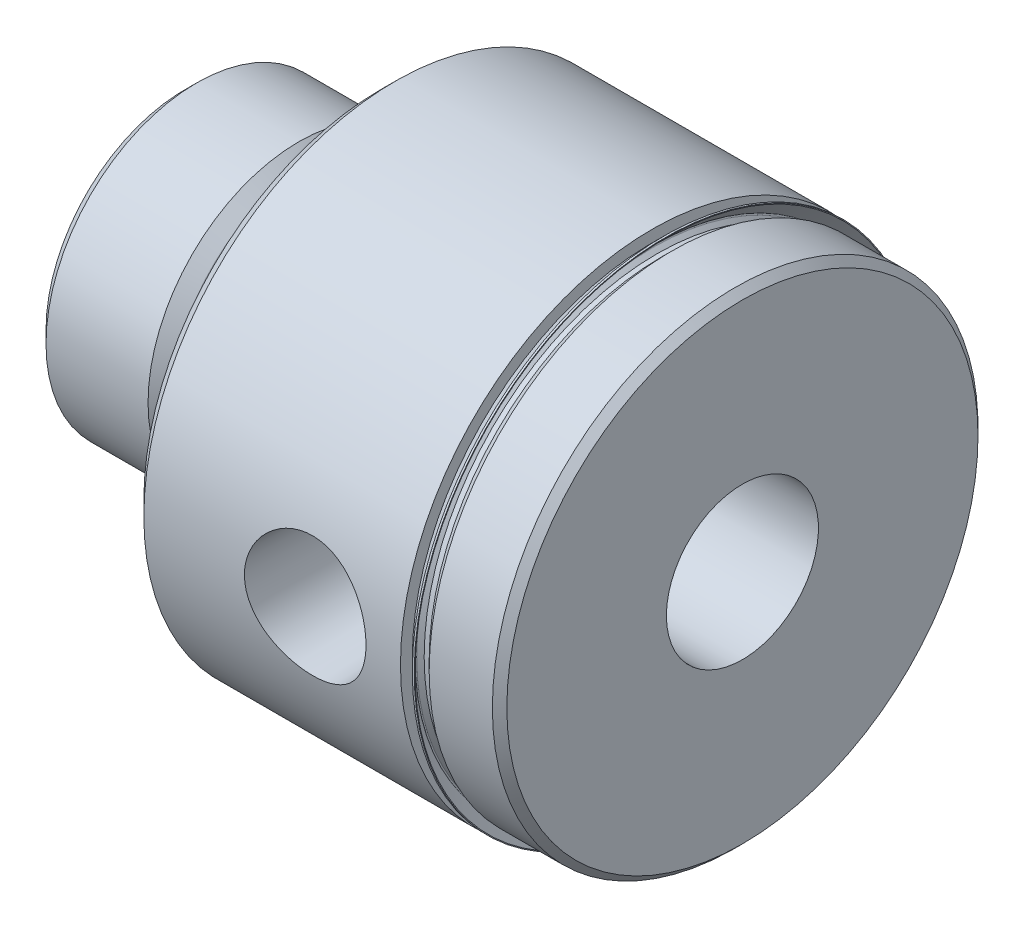
SolidWorks part; units mm, degrees
material "Cast Alloy Steel"
ref_plane "Front Plane" through (0, 0, 0) normal (0, 0, 1) x (1, 0, 0)
ref_plane "Top Plane" through (0, 0, 0) normal (0, 1, 0) x (1, 0, 0)
ref_plane "Right Plane" through (0, 0, 0) normal (1, 0, 0) x (0, 0, -1)
sketch "Sketch1" plane through (0, 0, 0) normal (0, 0, 1) x (1, 0, 0)
  line L0 (0, 0) -> (0, 14.6152)
  line L1 (0, 14.6152) -> (1.2598, 15.875)
  line L2 (1.2598, 15.875) -> (12.007, 15.875)
  line L3 (12.007, 15.875) -> (13.2834, 14.6412)
  line L4 (14.2367, 14.2558) -> (16.1036, 14.2558)
  line L5 (17.4752, 15.6274) -> (17.4752, 17.4434)
  line L6 (17.4752, 17.4434) -> (20.6502, 17.4434)
  line L7 (20.6502, 17.4434) -> (20.6502, 0)
  line L8 (20.6502, 0) -> (0, 0)
  line L9 (20.6502, 0) -> (0, 0) construction
  arc A0 (13.2834, 14.6412) -> (14.2367, 14.2558) centre (14.2367, 15.6273) ccw
  arc A1 (16.1036, 14.2558) -> (17.4752, 15.6274) centre (16.1036, 15.6274) ccw
revolve "Revolve1" add sketch "Sketch1" angle 360 about L9 reverse direction yes
cosmetic thread "Cosmetic Thread1" parameters "D1"=13.2668, "D2"=29.2303
sketch "Sketch2" plane through (0, 0, 0) normal (0, 0, 1) x (1, 0, 0)
  line L0 (20.6502, 0) -> (20.6502, 24.9618)
  line L1 (20.6502, 24.9618) -> (22.1742, 26.4858)
  line L2 (22.1742, 26.4858) -> (49.1998, 26.4858)
  line L3 (49.1998, 26.4858) -> (49.1998, 24.5174)
  line L4 (49.1998, 24.5174) -> (50.2539, 24.5174)
  line L5 (50.2539, 24.5174) -> (51.308, 25.5714)
  line L6 (51.308, 25.5714) -> (57.9628, 25.5714)
  line L7 (57.9628, 25.5714) -> (58.7248, 24.8095)
  line L8 (58.7248, 24.8095) -> (58.7248, 0)
  line L9 (58.7248, 0) -> (20.6502, 0)
  line L10 (58.7248, 0) -> (20.6502, 0) construction
revolve "Revolve2" add sketch "Sketch2" angle 360 about L10 reverse direction yes
hole_wizard "Hole1" positions "Sketch4" profile "Sketch3" legacy
sketch "Sketch4" plane through (0, 0, 0) normal (-1, 0, 0) x (0, 0, 1)
  point P0 (0, 0)
sketch "Sketch3" plane through (0, 0, 0) normal (0, 1, 0) x (0, 0, 1)
  line L0 (0, 0) -> (0, 58.7248)
  line L1 (0, 58.7248) -> (8.0074, 58.7248)
  line L2 (8.0074, 58.7248) -> (8.0074, 0.762)
  line L3 (8.0074, 0.762) -> (8.7694, 0)
  line L4 (8.7694, 0) -> (0, 0)
  line L5 (0, -6.4453) -> (0, 115.525) construction
  line L6 (-8.0074, 0.762) -> (-8.7694, 0) construction
  dimension "Diameter" = 16.0147
  dimension "Depth" = 58.7248
  dimension "C-Sink Angle" = 90
  dimension "C-Sink Diameter" = 17.5387
ref_plane "Plane1" through (0, 0, 0) normal (1, 0, 0) x (0, 0, -1)
ref_plane "Plane2" through (0, 0, 0) normal (1, 0, 0) x (0, 0, -1)
ref_plane "Plane3" through (0, 0, 0) normal (0, -0.7071, 0.7071) x (1, 0, 0)
ref_plane "Plane4" through (0, 0, 0) normal (1, 0, 0) x (0, 0, -1)
ref_plane "Plane5" through (49.2252, 0, 0) normal (1, 0, 0) x (0, 0, -1)
ref_plane "Plane6" through (20.6502, 0, 0) normal (1, 0, 0) x (0, 0, -1)
ref_plane "Plane7" through (49.2252, 0, 0) normal (1, 0, 0) x (0, 0, -1)
sketch "Sketch5" plane through (0, 0, 0) normal (0, 1, 0) x (1, 0, 0)
  line L0 (39.1668, 0) -> (42.3418, 0)
  line L1 (42.3418, 0) -> (42.3418, -8.9868)
  line L2 (42.3418, -8.9868) -> (45.1089, -11.7538)
  line L3 (45.1089, -11.7538) -> (45.5688, -26.4858)
  line L4 (45.5688, -26.4858) -> (39.1668, -26.4858)
  line L5 (39.1668, -26.4858) -> (39.1668, 0)
  line L6 (39.1668, -26.4858) -> (39.1668, 0) construction
revolve "Cut-Revolve1" cut sketch "Sketch5" angle 360 about L6 reverse direction yes
cosmetic thread "Cosmetic Thread2" parameters "D1"=8.8392, "D2"=13.716
sketch "Sketch6" plane through (0, 0, 0) normal (0, 0, 1) x (1, 0, 0)
  line L0 (49.1998, 24.2633) -> (50.2539, 24.2633)
  line L1 (50.2539, 24.2633) -> (50.2539, 24.5174)
  line L2 (50.2539, 24.5174) -> (49.7269, 24.5174)
  line L3 (49.7269, 24.5174) -> (49.3348, 24.9094)
  line L4 (49.3348, 25.089) -> (50.6475, 26.4017)
  line L5 (50.6475, 26.4017) -> (50.6475, 26.4858)
  line L6 (50.6475, 26.4858) -> (50.4443, 26.4858)
  line L7 (50.4443, 26.4858) -> (49.1998, 25.2413)
  line L8 (49.1998, 25.2413) -> (49.1998, 24.2633)
  line L9 (50.2539, 0) -> (49.1998, 0) construction
  arc A0 (49.3348, 24.9094) -> (49.3348, 25.089) centre (49.4246, 24.9992) cw
revolve "Revolve3" add sketch "Sketch6" angle 360 about L9 reverse direction yes
ref_plane "Plane8" through (50.2539, 0, 0) normal (1, 0, 0) x (0, 0, -1)
ref_plane "Plane9" through (20.6502, 0, 0) normal (1, 0, 0) x (0, 0, -1)
ref_plane "Plane10" through (17.4752, 0, 0) normal (1, 0, 0) x (0, 0, -1)
ref_plane "Plane11" through (0, 0, 0) normal (0, 1, 0) x (1, 0, 0)
ref_plane "Plane12" through (0, 0, 0) normal (0, 1, 0) x (1, 0, 0)
ref_plane "Plane13" through (20.6502, 0, 0) normal (1, 0, 0) x (0, 0, -1)
ref_plane "Plane14" through (0, 0, 0) normal (0, 0, 1) x (1, 0, 0)
ref_plane "Plane15" through (0, 0, 0) normal (0, 1, 0) x (1, 0, 0)
ref_plane "Plane16" through (0, 0, 0) normal (0, 1, 0) x (1, 0, 0)
ref_plane "Plane17" through (0, 0.1016, 0) normal (0, 1, 0) x (1, 0, 0)
ref_plane "Plane18" through (-12.7, 0, 0) normal (1, 0, 0) x (0, 0, -1)
ref_plane "dp1 XY" through (0, 0, 0) normal (0, 0, 1) x (1, 0, 0)
ref_plane "dp1 XZ" through (0, 17.4434, 0) normal (0, -1, 0) x (-1, 0, 0)
ref_plane "dp1 YZ" through (20.6502, 0, 0) normal (1, 0, 0) x (0, 0, -1)
ref_axis "dp1 X" through (-80.9, 17.4434, 0) along (1, 0, 0)
ref_axis "dp1 Y" through (20.6502, -50, 0) along (0, 1, 0)
ref_axis "dp1 Z" through (20.6502, 17.4434, 80.9) along (0, 0, -1)
sketch3d "dp1"
  point P0 (20.6502, 17.4434, 0)
ref_plane "dp2 XY" through (0, 0, 0) normal (0, 0, 1) x (1, 0, 0)
ref_plane "dp2 XZ" through (0, -17.4434, 0) normal (0, -1, 0) x (-1, 0, 0)
ref_plane "dp2 YZ" through (20.6502, 0, 0) normal (1, 0, 0) x (0, 0, -1)
ref_axis "dp2 X" through (-80.9, -17.4434, 0) along (1, 0, 0)
ref_axis "dp2 Y" through (20.6502, -50, 0) along (0, 1, 0)
ref_axis "dp2 Z" through (20.6502, -17.4434, 80.9) along (0, 0, -1)
sketch3d "dp2"
  point P0 (20.6502, -17.4434, 0)
ref_plane "port XY" through (0, 0, 0) normal (0, 0, 1) x (1, 0, 0)
ref_plane "port XZ" through (0, 0, 0) normal (0, -1, 0) x (-1, 0, 0)
ref_plane "port YZ" through (39.1668, 0, 0) normal (1, 0, 0) x (0, 0, -1)
ref_axis "port X" through (-80.9, 0, 0) along (1, 0, 0)
ref_axis "port Y" through (39.1668, -50, 0) along (0, 1, 0)
ref_axis "port Z" through (39.1668, 0, 80.9) along (0, 0, -1)
sketch3d "port"
  point P0 (39.1668, 0, 0)
ref_plane "rod_guide XY" through (0, 0, 0) normal (1, 0, 0) x (0, 0, -1)
ref_plane "rod_guide XZ" through (0, 0, 0) normal (0, -1, 0) x (-1, 0, 0)
ref_plane "rod_guide YZ" through (0, 0, 0) normal (0, 0, -1) x (-1, 0, 0)
ref_axis "rod_guide X" through (0, 0, 80.9) along (0, 0, -1)
ref_axis "rod_guide Y" through (0, -50, 0) along (0, 1, 0)
ref_axis "rod_guide Z" through (80.9, 0, 0) along (-1, 0, 0)
sketch3d "rod_guide"
  point P0 (0, 0, 0)
ref_plane "s1 XY" through (0, 0, 0) normal (0, 0, 1) x (1, 0, 0)
ref_plane "s1 XZ" through (0, 0, 0) normal (0, -1, 0) x (-1, 0, 0)
ref_plane "s1 YZ" through (17.4752, 0, 0) normal (1, 0, 0) x (0, 0, -1)
ref_axis "s1 X" through (-80.9, 0, 0) along (1, 0, 0)
ref_axis "s1 Y" through (17.4752, -50, 0) along (0, 1, 0)
ref_axis "s1 Z" through (17.4752, 0, 80.9) along (0, 0, -1)
sketch3d "s1"
  point P0 (17.4752, 0, 0)
ref_plane "s2 XY" through (0, 0, 0) normal (0, 0, 1) x (1, 0, 0)
ref_plane "s2 XZ" through (0, 0, 0) normal (0, -1, 0) x (-1, 0, 0)
ref_plane "s2 YZ" through (20.6502, 0, 0) normal (1, 0, 0) x (0, 0, -1)
ref_axis "s2 X" through (-80.9, 0, 0) along (1, 0, 0)
ref_axis "s2 Y" through (20.6502, -50, 0) along (0, 1, 0)
ref_axis "s2 Z" through (20.6502, 0, 80.9) along (0, 0, -1)
sketch3d "s2"
  point P0 (20.6502, 0, 0)
ref_plane "t1 XY" through (20.6502, 0, 0) normal (1, 0, 0) x (0, 0, -1)
ref_plane "t1 XZ" through (0, 0, 0) normal (0, -1, 0) x (-1, 0, 0)
ref_plane "t1 YZ" through (0, 0, 0) normal (0, 0, -1) x (-1, 0, 0)
ref_axis "t1 X" through (20.6502, 0, 80.9) along (0, 0, -1)
ref_axis "t1 Y" through (20.6502, -50, 0) along (0, 1, 0)
ref_axis "t1 Z" through (80.9, 0, 0) along (-1, 0, 0)
sketch3d "t1"
  point P0 (20.6502, 0, 0)
ref_plane "t111 XY" through (20.6502, 0, 0) normal (1, 0, 0) x (0, 0, -1)
ref_plane "t111 XZ" through (0, 0, 0) normal (0, -1, 0) x (-1, 0, 0)
ref_plane "t111 YZ" through (0, 0, 0) normal (0, 0, -1) x (-1, 0, 0)
ref_axis "t111 X" through (20.6502, 0, 80.9) along (0, 0, -1)
ref_axis "t111 Y" through (20.6502, -50, 0) along (0, 1, 0)
ref_axis "t111 Z" through (80.9, 0, 0) along (-1, 0, 0)
sketch3d "t111"
  point P0 (20.6502, 0, 0)
ref_plane "to_foot_bracket XY" through (20.6502, 0, 0) normal (1, 0, 0) x (0, 0, -1)
ref_plane "to_foot_bracket XZ" through (0, 0, 0) normal (0, -1, 0) x (-1, 0, 0)
ref_plane "to_foot_bracket YZ" through (0, 0, 0) normal (0, 0, -1) x (-1, 0, 0)
ref_axis "to_foot_bracket X" through (20.6502, 0, 80.9) along (0, 0, -1)
ref_axis "to_foot_bracket Y" through (20.6502, -50, 0) along (0, 1, 0)
ref_axis "to_foot_bracket Z" through (80.9, 0, 0) along (-1, 0, 0)
sketch3d "to_foot_bracket"
  point P0 (20.6502, 0, 0)
ref_plane "to_nut XY" through (17.4752, 0, 0) normal (1, 0, 0) x (0, 0, -1)
ref_plane "to_nut XZ" through (0, 0, 0) normal (0, -1, 0) x (-1, 0, 0)
ref_plane "to_nut YZ" through (0, 0, 0) normal (0, 0, -1) x (-1, 0, 0)
ref_axis "to_nut X" through (17.4752, 0, 80.9) along (0, 0, -1)
ref_axis "to_nut Y" through (17.4752, -50, 0) along (0, 1, 0)
ref_axis "to_nut Z" through (80.9, 0, 0) along (-1, 0, 0)
sketch3d "to_nut"
  point P0 (17.4752, 0, 0)
ref_plane "to_rod XY" through (-12.7, 0, 0) normal (1, 0, 0) x (0, 0, -1)
ref_plane "to_rod XZ" through (0, 0, 0) normal (0, -1, 0) x (-1, 0, 0)
ref_plane "to_rod YZ" through (0, 0, 0) normal (0, 0, -1) x (-1, 0, 0)
ref_axis "to_rod X" through (-12.7, 0, 80.9) along (0, 0, -1)
ref_axis "to_rod Y" through (-12.7, -50, 0) along (0, 1, 0)
ref_axis "to_rod Z" through (80.9, 0, 0) along (-1, 0, 0)
sketch3d "to_rod"
  point P0 (-12.7, 0, 0)
ref_plane "to_screw XY" through (0, 0.1016, 0) normal (0, 1, 0) x (1, 0, 0)
ref_plane "to_screw XZ" through (0, 0, -17.5895) normal (0, 0, 1) x (1, 0, 0)
ref_plane "to_screw YZ" through (39.1668, 0, 0) normal (1, 0, 0) x (0, 0, -1)
ref_axis "to_screw X" through (-80.9, 0.1016, -17.5895) along (1, 0, 0)
ref_axis "to_screw Y" through (39.1668, 0.1016, 50) along (0, 0, -1)
ref_axis "to_screw Z" through (39.1668, 50, -17.5895) along (0, -1, 0)
sketch3d "to_screw"
  point P0 (39.1668, 0.1016, -17.5895)
ref_plane "to_trunnion_brackets XY" through (0, 0, 0) normal (0, 1, 0) x (1, 0, 0)
ref_plane "to_trunnion_brackets XZ" through (0, 0, 0) normal (0, 0, 1) x (1, 0, 0)
ref_plane "to_trunnion_brackets YZ" through (0, 0, 0) normal (1, 0, 0) x (0, 0, -1)
ref_axis "to_trunnion_brackets X" through (-80.9, 0, 0) along (1, 0, 0)
ref_axis "to_trunnion_brackets Y" through (0, 0, 50) along (0, 0, -1)
ref_axis "to_trunnion_brackets Z" through (0, 50, 0) along (0, -1, 0)
sketch3d "to_trunnion_brackets"
  point P0 (0, 0, 0)
ref_plane "to_trunnion_brackets1 XY" through (0, 0, 0) normal (0, 1, 0) x (1, 0, 0)
ref_plane "to_trunnion_brackets1 XZ" through (0, 0, 0) normal (0, 0, 1) x (1, 0, 0)
ref_plane "to_trunnion_brackets1 YZ" through (0, 0, 0) normal (1, 0, 0) x (0, 0, -1)
ref_axis "to_trunnion_brackets1 X" through (-80.9, 0, 0) along (1, 0, 0)
ref_axis "to_trunnion_brackets1 Y" through (0, 0, 50) along (0, 0, -1)
ref_axis "to_trunnion_brackets1 Z" through (0, 50, 0) along (0, -1, 0)
sketch3d "to_trunnion_brackets1"
  point P0 (0, 0, 0)
ref_plane "to_trunnion_brackets2 XY" through (0, 0, 0) normal (0, 1, 0) x (1, 0, 0)
ref_plane "to_trunnion_brackets2 XZ" through (0, 0, 0) normal (0, 0, 1) x (1, 0, 0)
ref_plane "to_trunnion_brackets2 YZ" through (0, 0, 0) normal (1, 0, 0) x (0, 0, -1)
ref_axis "to_trunnion_brackets2 X" through (-80.9, 0, 0) along (1, 0, 0)
ref_axis "to_trunnion_brackets2 Y" through (0, 0, 50) along (0, 0, -1)
ref_axis "to_trunnion_brackets2 Z" through (0, 50, 0) along (0, -1, 0)
sketch3d "to_trunnion_brackets2"
  point P0 (0, 0, 0)
ref_plane "to_tube XY" through (50.2539, 0, 0) normal (1, 0, 0) x (0, 0, -1)
ref_plane "to_tube XZ" through (0, 0, 0) normal (0, -1, 0) x (-1, 0, 0)
ref_plane "to_tube YZ" through (0, 0, 0) normal (0, 0, -1) x (-1, 0, 0)
ref_axis "to_tube X" through (50.2539, 0, 80.9) along (0, 0, -1)
ref_axis "to_tube Y" through (50.2539, -50, 0) along (0, 1, 0)
ref_axis "to_tube Z" through (80.9, 0, 0) along (-1, 0, 0)
sketch3d "to_tube"
  point P0 (50.2539, 0, 0)
